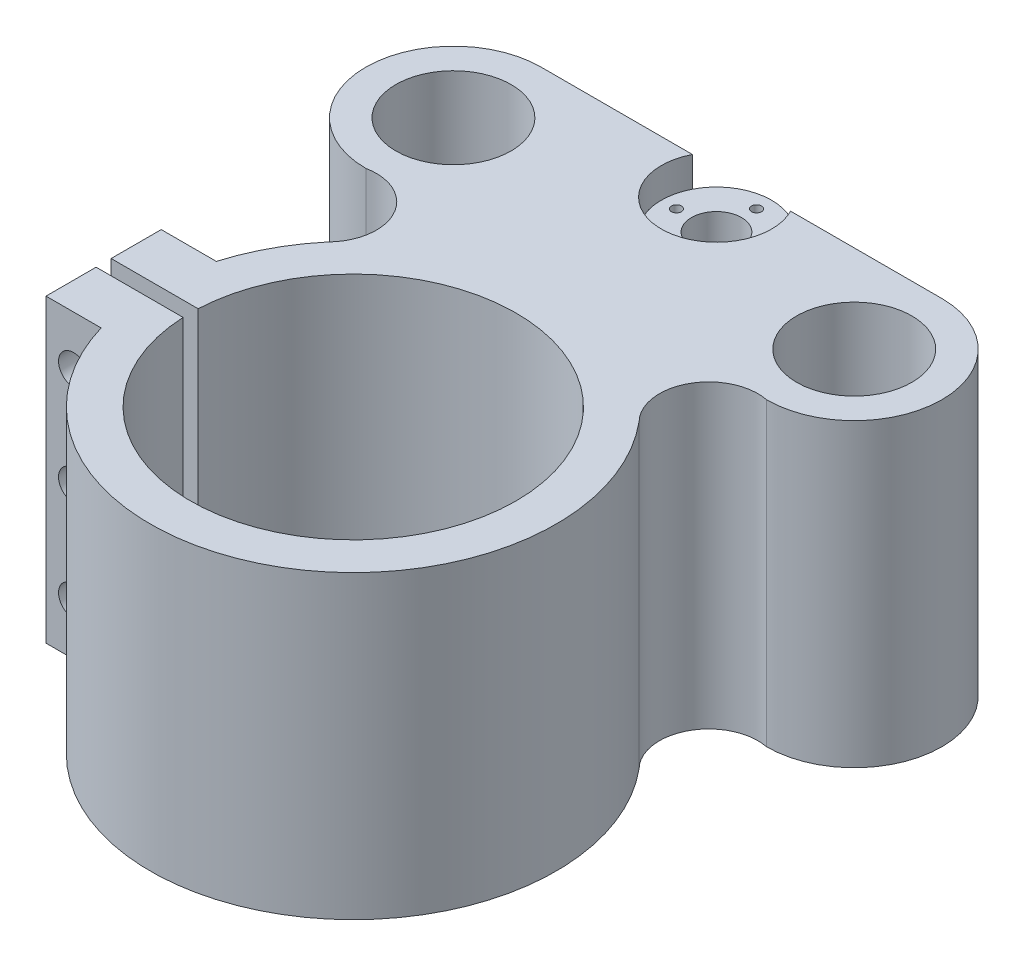
SolidWorks part; units mm, degrees
ref_plane "Front Plane" through (0, 0, 0) normal (0, 0, 1) x (1, 0, 0)
ref_plane "Top Plane" through (0, 0, 0) normal (0, 1, 0) x (1, 0, 0)
ref_plane "Right Plane" through (0, 0, 0) normal (1, 0, 0) x (0, 0, -1)
sketch "Sketch1" plane through (0, 0, 0) normal (0, 1, 0) x (1, 0, 0)
  line L0 (27.0908, 104.5706) -> (107.0908, 104.5706) construction
  line L3 (67.0908, 44.5706) -> (8.9284, 44.5706) construction
  line L5 (67.0908, 44.5706) -> (94.3328, 44.5706) construction
  line L6 (17.2579, 46.0706) -> (34.6255, 46.0706)
  line L7 (17.2579, 56.0706) -> (28.2579, 56.0706)
  line L8 (67.0908, 104.5706) -> (67.0908, 153.14) construction
  line L9 (67.0908, 111.1474) -> (67.0908, 30.162) construction
  line L10 (17.2579, 46.0706) -> (17.2579, 56.0706)
  line L11 (17.2579, 43.0706) -> (34.6255, 43.0706)
  line L12 (17.2579, 43.0706) -> (17.2579, 33.0706)
  line L14 (17.2579, 33.0706) -> (28.2579, 33.0706)
  line L15 (27.0908, 122.0706) -> (107.0908, 122.0706)
  circle A0 centre (27.0908, 104.5706) radius 11.5
  circle A2 centre (27.0908, 104.5706) radius 17.5
  arc A5 (34.6255, 43.0706) -> (34.6255, 46.0706) centre (67.0908, 44.5706) ccw
  arc A6 (28.2579, 33.0706) -> (28.2579, 56.0706) centre (67.0908, 44.5706) ccw
  circle A9 centre (67.0908, 44.5706) radius 32.5 construction
  circle A10 centre (67.0908, 44.5706) radius 40.5 construction
  arc A15 (27.0908, 87.0706) -> (36.0456, 70.5791) centre (29.015, 77.4384) cw
  arc A16 (107.0908, 87.0706) -> (98.1361, 70.5791) centre (105.1667, 77.4384) ccw
  circle A17 centre (107.0908, 104.5706) radius 11.5
  circle A18 centre (107.0908, 104.5706) radius 17.5
  point P25 (67.0908, 122.0706)
  dimension "D1" = 23
  dimension "D4" = 60
  dimension "D7" = 65
  dimension "D8" = 8
  dimension "D13" = 11
  dimension "D2" = 80
  dimension "D9" = 0
  dimension "D11" = 1.5
  dimension "D12" = 10
  dimension "D3" = 6
extrude "Boss-Extrude1" add sketch "Sketch1" along normal blind 60 contours A6 A5 | A2 A0 | A6 A2 | A2 A6 | A6 | A6 L10 | A6 | A18 A17 region at (18.4712, 0, -51.0706) region at (67.0908, 0, -101.1278) region at (28.2851, 0, -87.73) region at (90.1284, 0, -105.7735)
sketch "Sketch2" plane through (-1.1118, 0, -33.0706) normal (0, 0, 1) x (1, 0, 0)
  line L0 (30.4702, 30) -> (39.2061, 30) construction
  line L1 (18.3696, 60) -> (29.3696, 60) construction
  line L2 (29.3696, 60) -> (29.3696, 0) construction
  line L3 (23.8696, 39.9087) -> (23.8696, 20.4555) construction
  line L4 (18.3696, 60) -> (18.3696, 0) construction
  line L5 (18.3696, 0) -> (29.3696, 0) construction
  circle A0 centre (23.8696, 30) radius 3
  circle A1 centre (23.8696, 50) radius 3
  circle A2 centre (23.8696, 10) radius 3
  dimension "D1" = 6
  dimension "D2" = 2
  dimension "D3" = 20
extrude "Cut-Extrude1" cut sketch "Sketch2" against normal up to surface (23 mm away) and the other way through all up to face at (22.7579, 30, -56.0706)
sketch "Sketch3" plane through (0, 0, -56.0706) normal (0, 0, -1) x (-1, 0, 0)
  line L0 (-28.2579, 60) -> (-28.2579, 0) construction
  line L1 (-17.2579, 45) -> (-28.2579, 45)
  line L2 (-17.2579, 45) -> (-17.2579, 55)
  line L3 (-17.2579, 55) -> (-28.2579, 55)
  line L4 (-28.2579, 45) -> (-28.2579, 55)
  line L5 (-17.2579, 45) -> (-28.2579, 55) construction
  line L6 (-17.2579, 55) -> (-28.2579, 45) construction
  line L8 (-17.2579, 25) -> (-17.2579, 35)
  line L9 (-17.2579, 25) -> (-28.2579, 25)
  line L10 (-28.2579, 25) -> (-28.2579, 35)
  line L11 (-17.2579, 35) -> (-28.2579, 35)
  line L12 (-17.2579, 5) -> (-17.2579, 15)
  line L13 (-17.2579, 5) -> (-28.2579, 5)
  line L14 (-28.2579, 5) -> (-28.2579, 15)
  line L15 (-17.2579, 15) -> (-28.2579, 15)
  point P0 (-22.7579, 50)
  dimension "D1" = 10
  dimension "D2" = 3
extrude "Cut-Extrude2" cut sketch "Sketch3" against normal blind 5
sketch "Sketch5" plane through (0, 60, 0) normal (0, 1, 0) x (1, 0, 0)
  line L0 (27.0908, 104.5706) -> (107.3528, 104.5706) construction
  circle A0 centre (67.0908, 117.0706) radius 11
  circle A1 centre (67.0908, 117.0706) radius 5
  circle A2 centre (67.0908, 117.0706) radius 8 construction
  circle A3 centre (67.0908, 125.0706) radius 1
  circle A16 centre (75.0908, 117.0706) radius 1
  circle A17 centre (67.0908, 109.0706) radius 1
  circle A18 centre (59.0908, 117.0706) radius 1
  point P16 (67.0908, 103.0286)
  point P19 (69.5908, 109.5706)
  point P20 (71.6118, 102.5496)
  point P21 (69.5908, 114.5706)
  point P22 (67.0908, 117.0706)
  line M38 (107.0908, 122.0706) -> (27.0908, 122.0706)
  dimension "D1" = 10
  dimension "D2" = 2
  dimension "D4" = 16
  dimension "D5" = 22
  dimension "D6" = 12.5
  dimension "D3" = 4
extrude "Boss-Extrude2" add sketch "Sketch5" against normal blind 60 contours A0 A3 | A3 region at (56.402, 60, -117.0706) region at (67.0908, 60, -125.0706)
extrude "Cut-Extrude7" cut sketch "Sketch5<12>" against normal blind 6 contours A1 | A18 | A1 A0 A18 A17 A16 M38 | A0 A3 M38 | A3 | A16 | A17 region at (67.0908, 60, -117.0706) region at (64.5832, 60, -106.6398) region at (71.9898, 60, -122.2755) region at (67.0908, 60, -125.0706) region at (59.0908, 60, -117.0706)
sketch "Sketch5<12>" plane through (0, 60, 0) normal (0, 1, 0) x (1, 0, 0) same geometry as "Sketch5"
extrude "Cut-Extrude8" cut sketch "Sketch5<13>" against normal through all contours A1 region at (67.0908, 60, -117.0706)
sketch "Sketch5<13>" plane through (0, 60, 0) normal (0, 1, 0) x (1, 0, 0) same geometry as "Sketch5"
extrude "Cut-Extrude9" cut sketch "Sketch5<14>" against normal blind 6 from surface contours A3 | A18 | A17 | A16 starting at face at (67.0908, 54, -112.0706)
sketch "Sketch5<14>" plane through (0, 60, 0) normal (0, 1, 0) x (1, 0, 0) same geometry as "Sketch5"
